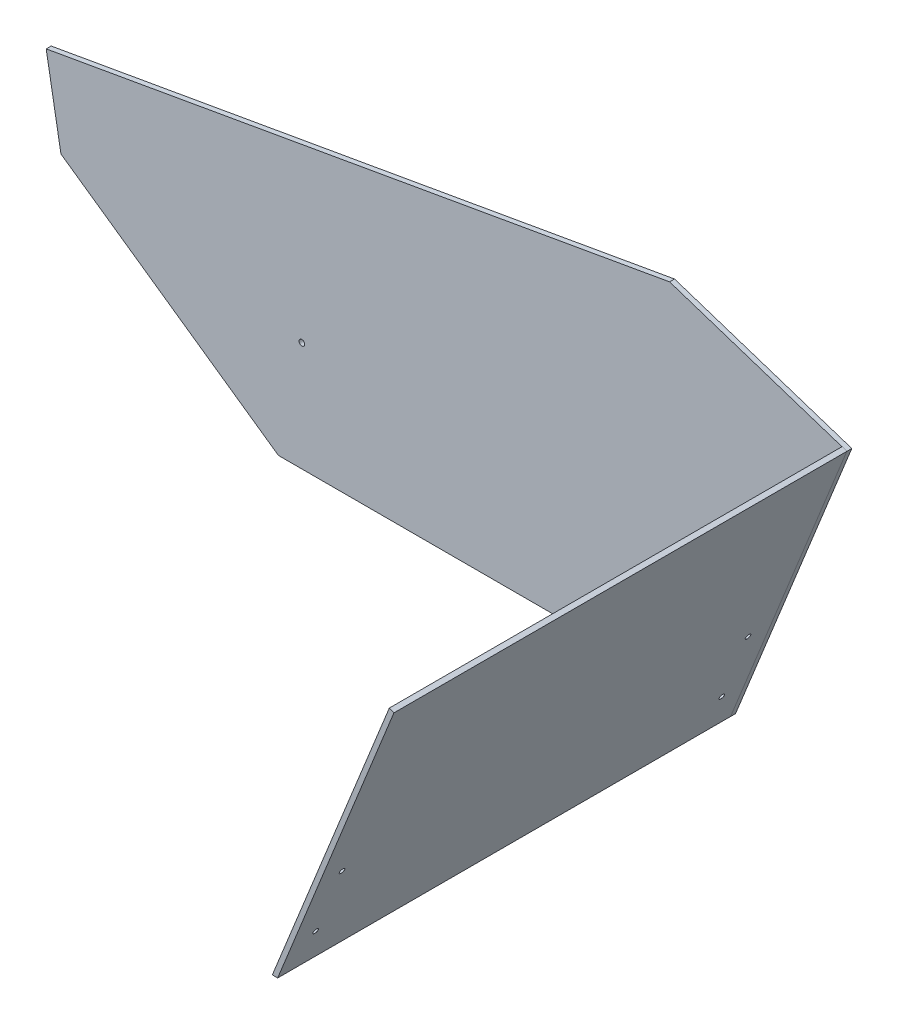
SolidWorks part; units mm, degrees
material "Melamine"
ref_plane "Front Plane" through (0, 0, 0) normal (0, 0, 1) x (1, 0, 0)
ref_plane "Top Plane" through (0, 0, 0) normal (0, 1, 0) x (1, 0, 0)
ref_plane "Right Plane" through (0, 0, 0) normal (1, 0, 0) x (0, 0, -1)
ref_axis "Axis1" through (0, 0, -14.8175) along (0, 0, 1)
sketch "Sketch1" plane through (0, 0, 0) normal (0, 0, 1) x (1, 0, 0)
  line L0 (-140, 0) -> (140, 0) construction
  line L1 (-140, 0) -> (-303.8304, 114.7153) construction
  line L4 (-151.0709, 0) -> (-307.4726, 109.5137) construction
  line L5 (-307.4726, 109.5137) -> (-303.8304, 114.7153) construction
  line L11 (140, 0) -> (143.4243, 0)
  line L12 (140, 0) -> (214.9213, 185.4368) construction
  line L14 (143.4243, 0) -> (217.8651, 184.2474)
  line L15 (217.8651, 184.2474) -> (214.9213, 185.4368)
  line L16 (214.9213, 185.4368) -> (140, 0)
  line L17 (-140, 0) -> (-151.0709, 0) construction
  point P4 (0, 0)
  dimension "D1" = 35
  dimension "D2" = 280
  dimension "D4" = 200
  dimension "D6" = 6.35
  dimension "D7" = 68
  dimension "D8" = 200
  dimension "D9" = 3.175
extrude "Boss-Extrude1" add sketch "Sketch1" along normal blind 290
sketch "Sketch2" plane through (0, 0, 0) normal (0, 0, 1) x (1, 0, 0)
  line L1 (-294.7779, 151.108) -> (104.3699, 221.4886)
  line L3 (143.4243, 0) -> (-146.0709, 0)
  line L4 (-146.0709, 0) -> (-285.3267, 97.508) construction
  line L5 (143.4243, 0) -> (217.8651, 184.2474)
  line L7 (-285.3267, 97.508) -> (-294.7779, 151.108)
  line L8 (-285.3267, 97.508) -> (-281.6845, 102.7096) construction
  line L9 (217.8651, 184.2474) -> (104.3699, 221.4886)
  line L10 (143.4243, 0) -> (104.3699, 221.4886) construction
  line L11 (-285.3267, 97.508) -> (-146.0709, 0)
  line L13 (-146.0709, 0) -> (-135, 0) construction
  line L14 (-285.3267, 97.508) -> (-146.0709, 0) construction
  line L15 (-281.6845, 102.7096) -> (-135, 0) construction
  dimension "D1" = 10
  dimension "D2" = 200
  dimension "D3" = 6.35
  dimension "D4" = 35
  dimension "D5" = 170
  dimension "D6" = 275
extrude "Boss-Extrude2" add sketch "Sketch2" against normal blind 3.175 separate body
ref_plane "HOLDING PLANE" through (0, 0, 0) normal (0.9848, 0.1736, 0) x (0, 0, 1)
ref_point "Walls Center"
hole_wizard "M3 Clearance Hole1" positions "Sketch3" profile "Sketch4" hole size "M3" standard "ANSI Metric" end condition through all
sketch "Sketch3" plane through (123.2976, -49.8155, 0) normal (0.9272, -0.3746, 0) x (0, 0, -1)
  line L0 (0, 53.7277) -> (0, 252.4449) construction
  line L1 (-290, 53.7277) -> (0, 53.7277) construction
  point P0 (-275, 123.7277)
  point P3 (-275, 78.7277)
  point P6 (-15, 123.7277)
  point P9 (-15, 78.7277)
  dimension "D1" = 15
  dimension "D2" = 25
sketch "Sketch4" plane through (169.6468, 64.9029, 275) normal (0, 0, 1) x (0.3746, 0.9272, 0)
  line L0 (0, 0) -> (0, 489.2651)
  line L1 (0, 489.2651) -> (1.7, 489.2651)
  line L2 (1.7, 489.2651) -> (1.7, 0.025)
  line L3 (1.7, 0.025) -> (1.725, 0)
  line L5 (1.725, 0) -> (0, 0)
  line L6 (-1.7, 0.025) -> (-1.725, 0) construction
  line L11 (0, -6.35) -> (0, 107.95) construction
  dimension "Thru Hole Dia." = 3.4
  dimension "Thru Hole Depth" = 489.2651
  dimension "Near C'Sink Dia." = 3.45
  dimension "Near C'Sink Angle" = 90
sketch "Sketch5" plane through (0, 0, -3.175) normal (0, 0, -1) x (-1, 0, 0)
  point P0 (-128.4243, 70)
  point P3 (131.0709, 70)
hole_wizard "M3 Clearance Hole2" positions "Sketch5" profile "Sketch6" hole size "M3" standard "ANSI Metric" end condition through all
sketch "Sketch6" plane through (128.4243, 70, -3.175) normal (1, 0, 0) x (0, 1, 0)
  line L0 (0, 0) -> (0, 293.175)
  line L1 (0, 293.175) -> (1.8, 293.175)
  line L2 (1.8, 293.175) -> (1.8, 0)
  line L5 (1.8, 0) -> (0, 0)
  line L11 (0, -6.35) -> (0, 107.95) construction
  dimension "Thru Hole Dia." = 3.6
  dimension "Thru Hole Depth" = 293.175
